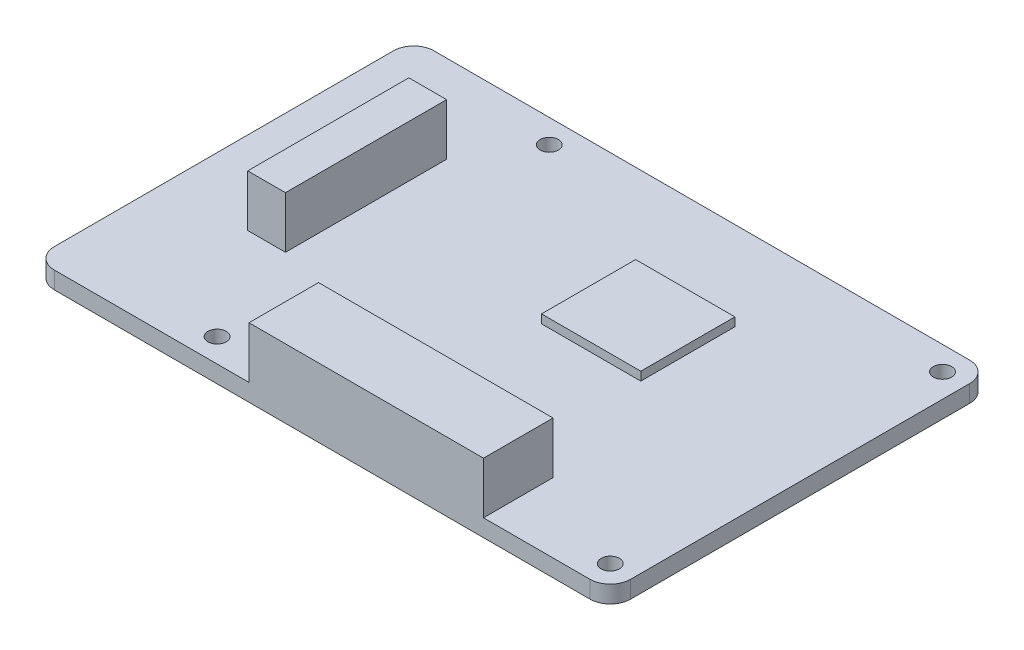
SolidWorks part; units mm, degrees
material "Silicon Dioxide"
ref_plane "Front" through (0, 0, 0) normal (0, 0, 1) x (1, 0, 0)
ref_plane "Top" through (0, 0, 0) normal (0, 1, 0) x (1, 0, 0)
ref_plane "Right" through (0, 0, 0) normal (1, 0, 0) x (0, 0, -1)
ref_axis "Axis1" through (0, 0, 55) along (0, 0, -1)
sketch "Sketch1" plane through (0, 0, 0) normal (0, 1, 0) x (1, 0, 0)
  line L0 (39.5, 28) -> (-39.5, 28)
  line L1 (-42.5, 25) -> (-42.5, -25)
  line L2 (-39.5, -28) -> (39.5, -28)
  line L3 (42.5, -25) -> (42.5, 25)
  circle A0 centre (39, -24.5) radius 3
  arc A1 (42.5, 25) -> (39.5, 28) centre (39.5, 25) ccw
  arc A2 (-39.5, 28) -> (-42.5, 25) centre (-39.5, 25) ccw
  arc A3 (-42.5, -25) -> (-39.5, -28) centre (-39.5, -25) ccw
  arc A4 (39.5, -28) -> (42.5, -25) centre (39.5, -25) ccw
  circle A5 centre (-19, 24.5) radius 3
  circle A6 centre (-19, 24.5) radius 1.35
  circle A7 centre (-19, -24.5) radius 1.35
  circle A8 centre (-19, -24.5) radius 3
  circle A9 centre (39, 24.5) radius 3
  circle A10 centre (39, 24.5) radius 1.35
  circle A11 centre (39, -24.5) radius 1.35
  dimension "D1" = 2.7
  dimension "D2" = 6
  dimension "D3" = 39
  dimension "D4" = 42.5
  dimension "D5" = 19
  dimension "D6" = 42.5
  dimension "D7" = 24.5
  dimension "D8" = 28
  dimension "D9" = 24.5
  dimension "D10" = 28
extrude "Boss-Extrude1" add sketch "Sketch1" along normal blind 2.54 contours A8 A7 | A5 A6 | L2 A4 L3 A1 L0 A2 L1 A3 A9 A8 A5 A0 | A9 A10 | A0 A11 region at (-0.2438, 0, 0) region at (36.0849, 0, 24.5) region at (-21.9151, 0, -24.5) region at (-21.9151, 0, 24.5) region at (36.0849, 0, -24.5)
sketch "Sketch2" plane through (0, 2.54, 0) normal (0, 1, 0) x (1, 0, 0)
  line L0 (-39.5, -28) -> (39.5, -28) construction
  line L1 (-10.7963, -17.7403) -> (23.7946, -17.7403)
  line L2 (-10.7963, -17.7403) -> (-10.7963, -28)
  line L3 (-10.7963, -28) -> (23.7946, -28)
  line L4 (23.7946, -17.7403) -> (23.7946, -28)
  line L5 (-10.7963, -17.7403) -> (23.7946, -28) construction
  line L6 (-10.7963, -28) -> (23.7946, -17.7403) construction
  line L7 (42.5, -25) -> (42.5, 25) construction
  point P4 (6.4992, -22.8702)
  dimension "D1" = 18.7054
  dimension "D2" = 36.0008
  dimension "D3" = 5.1298
extrude "Boss-Extrude2" add sketch "Sketch2" along normal blind 7.62
sketch "Sketch3" plane through (0, 2.54, 0) normal (0, 1, 0) x (1, 0, 0)
  line L0 (42.5, -25) -> (42.5, 25) construction
  line L1 (-24.721, 15.078) -> (-30.2919, 15.078)
  line L2 (-24.721, 15.078) -> (-24.721, -8.6912)
  line L3 (-24.721, -8.6912) -> (-30.2919, -8.6912)
  line L4 (-30.2919, 15.078) -> (-30.2919, -8.6912)
  line L5 (-24.721, 15.078) -> (-30.2919, -8.6912) construction
  line L6 (-24.721, -8.6912) -> (-30.2919, 15.078) construction
  line L7 (39.5, 28) -> (-39.5, 28) construction
  point P4 (-27.5064, 3.1934)
  dimension "D1" = 67.221
  dimension "D2" = 70.0064
  dimension "D3" = 12.922
  dimension "D4" = 24.8066
extrude "Boss-Extrude3" add sketch "Sketch3" along normal blind 7.62
sketch "Sketch4" plane through (0, 2.54, 0) normal (0, 1, 0) x (1, 0, 0)
  line L1 (3.2966, 14.9369) -> (17.9361, 14.9369)
  line L2 (3.2966, 14.9369) -> (3.2966, 1.0575)
  line L3 (3.2966, 1.0575) -> (17.9361, 1.0575)
  line L4 (17.9361, 14.9369) -> (17.9361, 1.0575)
  line L5 (3.2966, 14.9369) -> (17.9361, 1.0575) construction
  line L6 (3.2966, 1.0575) -> (17.9361, 14.9369) construction
  point P4 (10.6164, 7.9972)
extrude "Boss-Extrude4" add sketch "Sketch4" along normal blind 1.27
